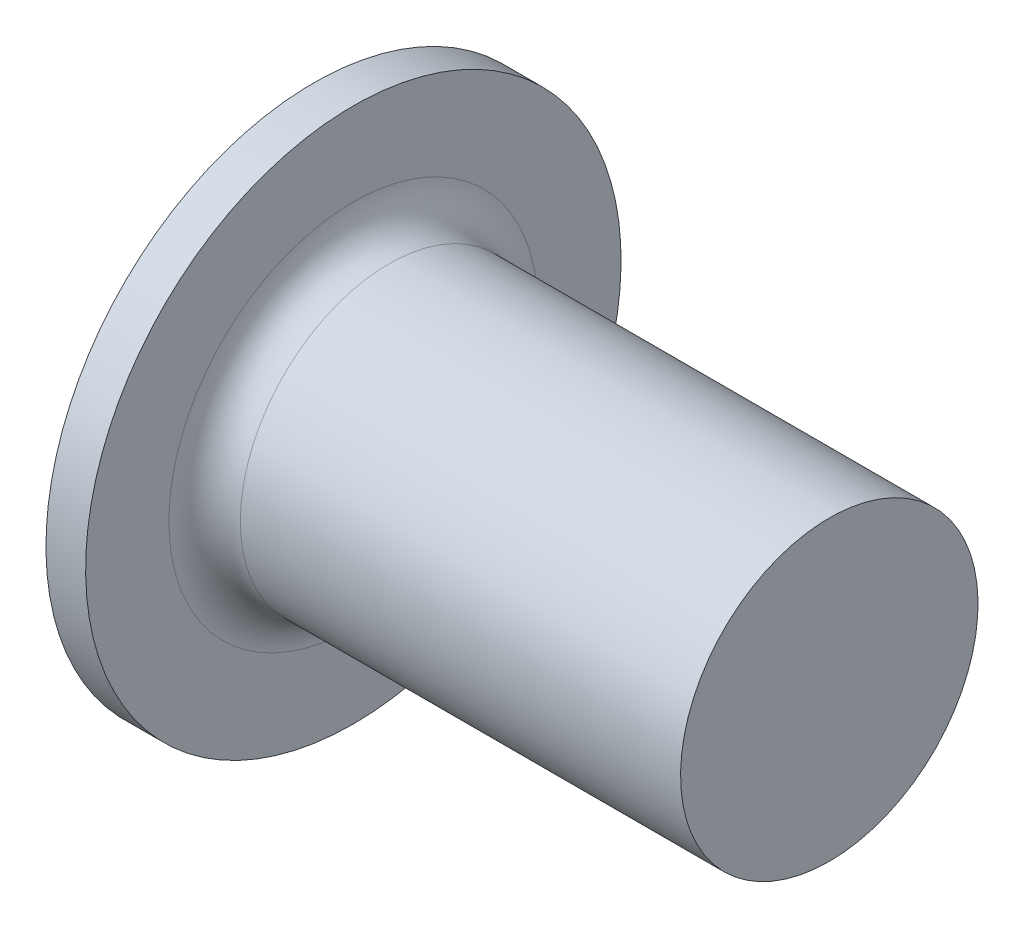
SolidWorks part; units mm, degrees
material "AISI 304"
ref_plane "Front Plane" through (0, 0, 0) normal (0, 0, 1) x (1, 0, 0)
ref_plane "Top Plane" through (0, 0, 0) normal (0, 1, 0) x (1, 0, 0)
ref_plane "Right Plane" through (0, 0, 0) normal (1, 0, 0) x (0, 0, -1)
ref_plane "Plane1" through (-1, 0, 0) normal (1, 0, 0) x (0, 0, -1)
sketch "Sketch1" plane through (0, 0, 0) normal (0, 0, 1) x (1, 0, 0)
  line L0 (-1, 0) -> (8, 0) construction
  line L1 (0, 2.5) -> (8, 2.5)
  line L2 (8, 2.5) -> (8, 0)
  line L3 (8, 0) -> (-1, 0)
  line L4 (-1, 0) -> (-1, 3.9226)
  line L5 (-1, 3.9226) -> (-0.6667, 4.5)
  line L6 (-0.6667, 4.5) -> (0, 4.5)
  line L7 (0, 4.5) -> (0, 2.5)
  dimension "M" = 5
  dimension "L" = 8
  dimension "FIX_1" = 30
  dimension "A" = 9
  dimension "E" = 1
  dimension "KSS_1" = 0.6667
revolve "Revolve1" add sketch "Sketch1" angle 360 about L0
cosmetic thread "Thread1" parameters "ATD"=4.134
chamfer "Chamfer1" [suppressed] distance 0.2 angle 45
sketch "Sketch2" plane through (-1, 0, 0) normal (1, 0, 0) x (0, 0, -1)
  line L0 (0, 1.4) -> (0, -1.4) construction
  line L1 (1.4, 0) -> (-1.4, 0) construction
  line L2 (1.2124, 0.7) -> (-1.2124, -0.7) construction
  line L3 (-1.2124, 0.7) -> (1.2124, -0.7) construction
  line L4 (0.7, 1.2124) -> (-0.7, -1.2124) construction
  line L5 (-0.7, 1.2124) -> (0.7, -1.2124) construction
  circle A0 centre (0, 0) radius 1.4 construction
  circle A1 centre (0, 0) radius 1.025 construction
  arc A2 (0.2688, 1.1983) -> (-0.2688, 1.1983) centre (0, 1.12) ccw
  arc A3 (1.1721, 0.3663) -> (0.9033, 0.832) centre (0.9699, 0.56) ccw
  arc A4 (0.9033, -0.832) -> (1.1721, -0.3663) centre (0.9699, -0.56) ccw
  arc A5 (-0.2688, -1.1983) -> (0.2688, -1.1983) centre (0, -1.12) ccw
  arc A6 (-1.1721, -0.3663) -> (-0.9033, -0.832) centre (-0.9699, -0.56) ccw
  arc A7 (-0.9033, 0.832) -> (-1.1721, 0.3663) centre (-0.9699, 0.56) ccw
  arc A8 (0.2688, 1.1983) -> (0.9033, 0.832) centre (0.7773, 1.3463) ccw
  arc A9 (1.1721, 0.3663) -> (1.1721, -0.3663) centre (1.5545, 0) ccw
  arc A10 (0.9033, -0.832) -> (0.2688, -1.1983) centre (0.7773, -1.3463) ccw
  arc A11 (-0.2688, -1.1983) -> (-0.9033, -0.832) centre (-0.7773, -1.3463) ccw
  arc A12 (-1.1721, -0.3663) -> (-1.1721, 0.3663) centre (-1.5545, 0) ccw
  arc A13 (-0.9033, 0.832) -> (-0.2688, 1.1983) centre (-0.7773, 1.3463) ccw
  dimension "MSM_1" = 2.8
  dimension "MSM_2" = 2.05
  dimension "MSM_3" = 0.28
  dimension "FIX_5" = 30
  dimension "FIX_6" = 30
  dimension "FIX_7" = 60
  dimension "FIX_8" = 60
extrude "Cut-Extrude1" cut sketch "Sketch2" along normal blind 1
fillet "Fillet1" radius 0.6 1 edges at (0, -2.5, 0)
equation "\"KSS_1@Sketch1\"= \"E@Sketch1\" * 2 / 3"
